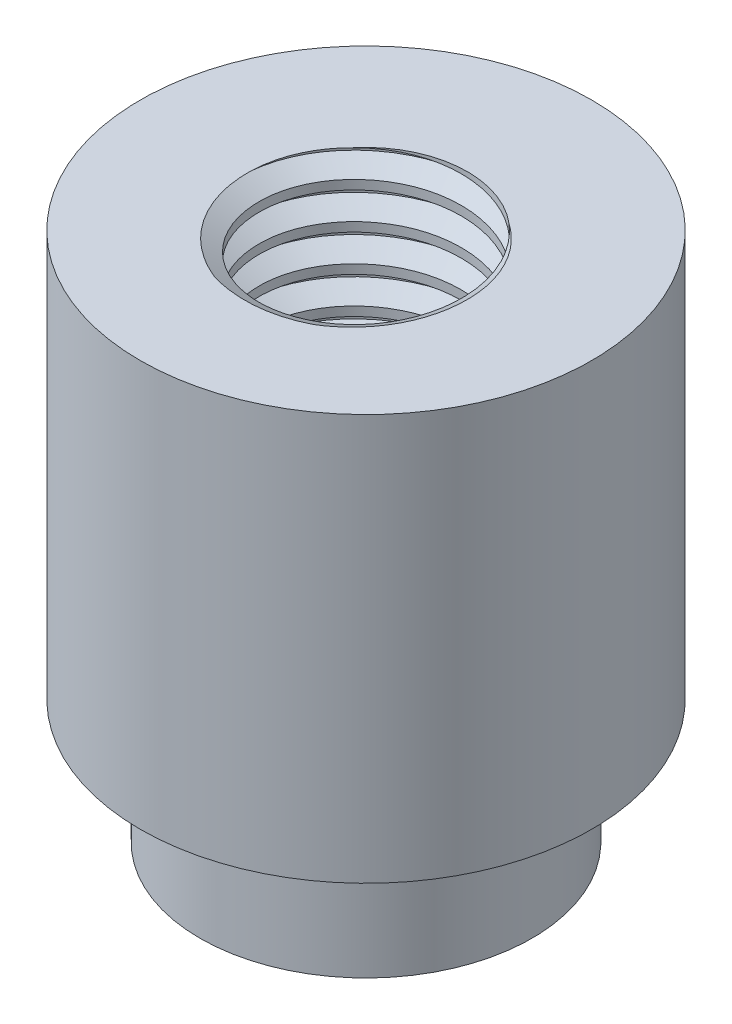
SolidWorks part; units mm, degrees
ref_plane "Front Plane" through (0, 0, 0) normal (0, 0, 1) x (1, 0, 0)
ref_plane "Top Plane" through (0, 0, 0) normal (0, 1, 0) x (1, 0, 0)
ref_plane "Right Plane" through (0, 0, 0) normal (1, 0, 0) x (0, 0, -1)
sketch "Sketch1" plane through (0, 0, 0) normal (0, 1, 0) x (1, 0, 0)
  circle A0 centre (0, 0) radius 2.78
  dimension "D1" = 5.56
extrude "Boss-Extrude1" add sketch "Sketch1" along normal blind 5 and the other way blind 1.53
sketch "Sketch2" plane through (0, -1.53, 0) normal (0, -1, 0) x (1, 0, 0)
  circle A0 centre (0, 0) radius 2.045
  dimension "D1" = 4.09
extrude "Cut-Extrude1" cut sketch "Sketch2" against normal up to surface (1.53 mm away) flip side to cut up to plane "Top Plane"
sketch "Sketch3" plane through (0, 5, 0) normal (0, 1, 0) x (1, 0, 0)
  circle A0 centre (0, 0) radius 1.25
  dimension "D1" = 2.5
extrude "Cut-Extrude2" cut sketch "Sketch3" against normal up to next
thread "Thread1" pitch 0.45 method cut profile "Thread Profile1" start angle 0, offset 0.5, length 0, pitch 0.45, diameter 2.5
ref_plane "Plane1" through (-1.25, 5.5, 0) normal (0, 0, 1) x (-1, 0, 0)
sketch "Thread Profile1" plane through (-1.25, 5.5, 0) normal (0, 0, 1) x (-1, 0, 0)
  line L0 (0, 0) -> (0, 0.45) construction
  line L1 (0, 0) -> (0.2436, 0.1406)
  line L2 (0.2436, 0.1406) -> (0.2436, 0.1969)
  line L3 (0.2436, 0.1969) -> (0, 0.3375)
  line L4 (0.2436, 0.1687) -> (0, 0.1687) construction
  line L11 (0, 0) -> (0, 0.3375)
  point P2 (0, 0)
  dimension "Pitch" = 0.45
  dimension "Profile_Angle" = 60
  dimension "Profile_Land" = 0.0562
  dimension "Profile_Height" = 0.2436
